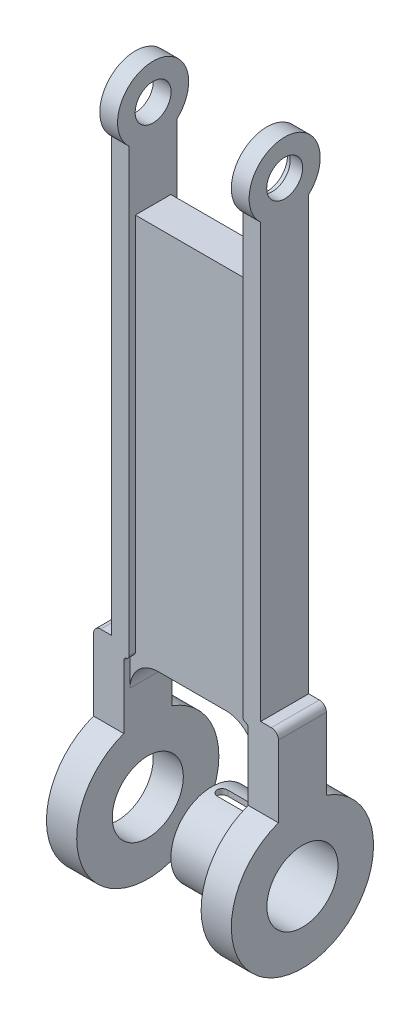
SolidWorks part; units mm, degrees
ref_plane "Alzado" through (0, 0, 0) normal (0, 0, 1) x (1, 0, 0)
ref_plane "Planta" through (0, 0, 0) normal (0, 1, 0) x (1, 0, 0)
ref_plane "Vista lateral" through (0, 0, 0) normal (1, 0, 0) x (0, 0, -1)
sketch "Croquis1" plane through (0, 0, 0) normal (0, 0, 1) x (1, 0, 0)
  line L0 (0, 0) -> (0, -143)
  line L1 (0, 0) -> (-1.6, 0)
  line L2 (-42, 0) -> (-42, -143)
  line L4 (-42, -35) -> (0, -35)
  line L5 (-42, -143) -> (0, -143)
  line L6 (-42, 0) -> (-37.4, 0)
  line L7 (-37.4, 0) -> (-37.4, -35)
  line L8 (-1.6, 0) -> (-1.6, -35)
  line L9 (-37.4, 0) -> (-42, 0)
  dimension "D1" = 42
extrude "Saliente-Extruir1" add sketch "Croquis1" against normal blind 10 contours L4 L5 region at (-21, -89, 0)
sketch "Croquis3" plane through (0, 0, 0) normal (0, 0, 1) x (1, 0, 0)
  line L0 (-47, -145) -> (-47, -160)
  line L1 (-47, -200) -> (-47, -180) construction
  line L2 (-47, -145) -> (-47, -141)
  line L4 (-47, -180) -> (-30.5, -180) construction
  line L5 (-42, -35) -> (-42, 0)
  line L6 (5, -143) -> (5, -200)
  line L7 (-47, -200) -> (-47, -180)
  line L8 (-30.5, -180) -> (-30.5, -143) construction
  line L9 (-42, -143) -> (0, -143) construction
  line L10 (-47, -180) -> (-47, -200)
  line L11 (-47, -180) -> (-47, -160)
  line L12 (-3.5, -151) -> (-3.5, -200)
  line L13 (-38.5, -200) -> (-38.5, -151)
  line L14 (5, -143) -> (5, -141)
  line L15 (-47, -200) -> (-38.5, -200)
  line L16 (-3.5, -200) -> (5, -200)
  line L17 (-45, -139) -> (-42, -139)
  line L18 (-42, -35) -> (-42, -143) construction
  line L19 (-30.5, -143) -> (-11.5, -143)
  line L20 (3, -139) -> (0, -139)
  line L21 (0, -35) -> (0, -143) construction
  line L22 (-30.5, -143) -> (-38.5, -143)
  line L23 (-38.5, -143) -> (-38.5, -151)
  line L24 (-30.5, -143) -> (-38.5, -143)
  arc A0 (5, -141) -> (3, -139) centre (3, -141) ccw
  arc A1 (-45, -139) -> (-47, -141) centre (-45, -141) ccw
  arc A2 (-11.5, -143) -> (-3.5, -151) centre (-11.5, -151) cw
  arc A3 (-38.5, -151) -> (-30.5, -143) centre (-30.5, -151) cw
  point P7 (5, -143)
  point P14 (10, -143)
  point P27 (-47, -143)
  point P29 (-49.26, -143)
  point P31 (7.26, -143)
  line M12 (-42, -35) -> (-42, -143)
  line M13 (-42, -143) -> (0, -143)
  line M14 (0, -143) -> (0, -35)
  dimension "D1" = 8.5
  dimension "D3" = 2
  dimension "D6" = 2
  dimension "D5" = 8
  dimension "D2" = 165
  dimension "D4" = 35
  dimension "D7" = 8.5
sketch "Croquis20" plane through (0, -35, 0) normal (0, 1, 0) x (1, 0, 0)
extrude "Saliente-Extruir2" add sketch "Croquis3" against normal blind 10 contours L17 A1 L2 L0 L11 L7 L15 L13 L23 M13 M12 | A2 L12 L16 L6 L14 A0 L20 M13 M14 region at (-42.813, -170.3435, 0) region at (0.6511, -169.665, 0)
sketch "Croquis21" plane through (0, 0, 0) normal (0, 0, 1) x (1, 0, 0)
  line L0 (-47, -145) -> (-47, -160)
  line L1 (-47, -200) -> (-47, -180) construction
  line L2 (-47, -145) -> (-47, -141)
  line L4 (-47, -180) -> (-30.5, -180) construction
  line L5 (-42, -35) -> (-42, 0)
  line L6 (5, -143) -> (5, -200)
  line L7 (-47, -200) -> (-47, -180)
  line L8 (-30.5, -180) -> (-30.5, -143) construction
  line L10 (-47, -180) -> (-47, -200)
  line L11 (-47, -180) -> (-47, -160)
  line L12 (-3.5, -151) -> (-3.5, -200)
  line L13 (-38.5, -200) -> (-38.5, -151)
  line L14 (5, -143) -> (5, -141)
  line L15 (-47, -200) -> (-38.5, -200)
  line L16 (-3.5, -200) -> (5, -200)
  line L17 (-45, -139) -> (-42, -139)
  line L19 (-30.5, -143) -> (-11.5, -143)
  line L20 (3, -139) -> (0, -139)
  line L22 (-30.5, -143) -> (-38.5, -143)
  line L23 (-38.5, -143) -> (-38.5, -151)
  line L24 (-30.5, -143) -> (-38.5, -143)
  arc A0 (5, -141) -> (3, -139) centre (3, -141) ccw
  arc A1 (-45, -139) -> (-47, -141) centre (-45, -141) ccw
  arc A2 (-11.5, -143) -> (-3.5, -151) centre (-11.5, -151) cw
  arc A3 (-38.5, -151) -> (-30.5, -143) centre (-30.5, -151) cw
  point P7 (5, -143)
  point P14 (10, -143)
  point P27 (-47, -143)
  point P29 (-49.26, -143)
  point P31 (7.26, -143)
  dimension "D1" = 8.5
  dimension "D3" = 2
  dimension "D6" = 2
  dimension "D5" = 8
  dimension "D4" = 35
  dimension "D7" = 8.5
extrude "Saliente-Extruir3" add sketch "Croquis21" against normal blind 10 contours L23 A3 L22 region at (-36.7131, -144.7869, 0)
sketch "Croquis22" plane through (0, 0, -10) normal (0, 0, -1) x (-1, 0, 0)
  line L0 (3.5, -156.8736) -> (3.5, -141.3338)
  line L1 (38.5, -155.5125) -> (38.5, -141.3338)
  line L2 (3.5, -151) -> (3.5, -200) construction
  line L3 (5, -139.3973) -> (5, -35)
  line L4 (42, -35) -> (0, -35) construction
  line L5 (0, -35) -> (0, -139) construction
  line L6 (5, -35) -> (0, -35)
  line L7 (38.5, -200) -> (38.5, -151) construction
  line L8 (37, -35) -> (37, -139.3973)
  line L9 (42, -35) -> (42, -139) construction
  line L10 (0, -35) -> (0, -139)
  line L11 (0, -139) -> (-3, -139)
  line L12 (45, -139) -> (42, -139) construction
  line L13 (47, -200) -> (47, -141) construction
  line L14 (47, -200) -> (38.5, -200) construction
  line L15 (3.5, -200) -> (-5, -200) construction
  line L16 (-5, -141) -> (-5, -200) construction
  line L17 (42, -35) -> (0, -35)
  line L18 (42, -35) -> (42, -139)
  line L19 (45, -139) -> (42, -139)
  line L20 (47, -200) -> (47, -141)
  line L21 (38.5, -200) -> (38.5, -151)
  line L22 (47, -200) -> (38.5, -200)
  line L23 (3.5, -200) -> (-5, -200)
  line L24 (-5, -141) -> (-5, -200)
  arc A0 (4.25, -140.3655) -> (3.5, -141.3338) centre (4.5, -141.3338) ccw
  arc A1 (4.25, -140.3655) -> (5, -139.3973) centre (4, -139.3973) ccw
  arc A2 (37.75, -140.3655) -> (37, -139.3973) centre (38, -139.3973) cw
  arc A3 (38.5, -141.3338) -> (37.75, -140.3655) centre (37.5, -141.3338) ccw
  arc A4 (47, -141) -> (45, -139) centre (45, -141) ccw construction
  arc A5 (-3, -139) -> (-5, -141) centre (-3, -141) ccw construction
  arc A6 (47, -141) -> (45, -139) centre (45, -141) ccw
  arc A7 (-3, -139) -> (-5, -141) centre (-3, -141) ccw
  line M10 (38.5, -151) -> (38.5, -200)
  line M11 (38.5, -200) -> (47, -200)
  line M12 (47, -200) -> (47, -141)
  arc M13 (47, -141) -> (45, -139) centre (45, -141) ccw
  line M14 (45, -139) -> (42, -139)
  line M15 (42, -139) -> (42, -35)
  line M16 (42, -35) -> (0, -35)
  line M17 (0, -35) -> (0, -139)
  line M18 (0, -139) -> (-3, -139)
  arc M19 (-3, -139) -> (-5, -141) centre (-3, -141) ccw
  line M20 (-5, -141) -> (-5, -200)
  line M21 (-5, -200) -> (3.5, -200)
  line M22 (3.5, -200) -> (3.5, -151)
  dimension "D2" = 1
  dimension "D3" = 1
  dimension "D5" = 1
  dimension "D6" = 1
  dimension "D1" = 5
  dimension "D4" = 5
extrude "Saliente-Extruir4" add sketch "Croquis22" along normal blind 1.75 contours A0 A1 L3 L0 M16 M17 M18 M19 M20 M21 M22 | A3 L1 L8 A2 M10 M11 M12 M13 M14 M15 M16 region at (-0.8883, -128.2038, -10) region at (-41.1117, -128.2038, -10)
sketch "Croquis24" plane through (0, 0, 0) normal (0, 0, 1) x (1, 0, 0)
  line L0 (-37, -35) -> (-37, -138.9269)
  line L1 (-42, -35) -> (0, -35) construction
  line L2 (-5, -35) -> (-5, -138.9269)
  line L3 (-42, -35) -> (-42, -139) construction
  line L4 (0, -35) -> (0, -139) construction
  line L5 (-38.5, -156.0308) -> (-38.5, -143.4351)
  line L6 (-38.5, -200) -> (-38.5, -151) construction
  line L7 (-3.5, -141.3338) -> (-3.5, -151) construction
  line L8 (-3.5, -151) -> (-3.5, -200) construction
  line L9 (-3.5, -151) -> (-3.5, -142.3338)
  line L10 (-37, -141.4986) -> (-37, -138.9269)
  line L11 (-5, -140.3973) -> (-5, -138.9269)
  line L12 (-3.5, -200) -> (5, -200) construction
  line L13 (5, -141) -> (5, -200) construction
  line L14 (3, -139) -> (0, -139) construction
  line L15 (-45, -139) -> (-42, -139) construction
  line L16 (-47, -200) -> (-47, -141) construction
  line L17 (-47, -200) -> (-38.5, -200) construction
  line L18 (-3.5, -151) -> (-3.5, -200)
  line L19 (-3.5, -200) -> (5, -200)
  line L20 (5, -141) -> (5, -200)
  line L21 (3, -139) -> (0, -139)
  line L22 (0, -35) -> (0, -139)
  line L23 (-42, -35) -> (-37, -35)
  line L24 (-42, -35) -> (-42, -139)
  line L25 (-45, -139) -> (-42, -139)
  line L26 (-47, -200) -> (-47, -141)
  line L27 (-47, -200) -> (-38.5, -200)
  line L28 (-38.5, -200) -> (-38.5, -151)
  line L29 (-5, -35) -> (0, -35)
  arc A0 (-4.25, -141.3655) -> (-5, -140.3973) centre (-4, -140.3973) cw
  arc A1 (-4.25, -141.3655) -> (-3.5, -142.3338) centre (-4.5, -142.3338) cw
  arc A2 (-37, -141.4986) -> (-37.75, -142.4669) centre (-38, -141.4986) cw
  arc A3 (-37.75, -142.4669) -> (-38.5, -143.4351) centre (-37.5, -143.4351) ccw
  arc A4 (5, -141) -> (3, -139) centre (3, -141) ccw construction
  arc A5 (-45, -139) -> (-47, -141) centre (-45, -141) ccw construction
  arc A6 (5, -141) -> (3, -139) centre (3, -141) ccw
  arc A7 (-45, -139) -> (-47, -141) centre (-45, -141) ccw
  point P28 (-37, -142.4986)
  line M6 (-3.5, -151) -> (-3.5, -200)
  line M7 (-3.5, -200) -> (5, -200)
  line M8 (5, -200) -> (5, -141)
  arc M9 (5, -141) -> (3, -139) centre (3, -141) ccw
  line M10 (3, -139) -> (0, -139)
  line M11 (0, -139) -> (0, -35)
  line M12 (0, -35) -> (-42, -35)
  line M13 (-42, -35) -> (-42, -139)
  line M14 (-42, -139) -> (-45, -139)
  arc M15 (-45, -139) -> (-47, -141) centre (-45, -141) ccw
  line M16 (-47, -141) -> (-47, -200)
  line M17 (-47, -200) -> (-38.5, -200)
  line M18 (-38.5, -200) -> (-38.5, -151)
  dimension "D3" = 1
  dimension "D4" = 1
  dimension "D5" = 1
  dimension "D6" = 1
  dimension "D1" = 5
  dimension "D2" = 5
extrude "Saliente-Extruir5" add sketch "Croquis24" along normal blind 1.75 contours A3 A2 L10 L0 L5 M12 M13 M14 M15 M16 M17 M18 | A0 A1 L9 L2 L11 M6 M7 M8 M9 M10 M11 M12 region at (-41.1016, -128.2438, 0) region at (-0.8931, -128.2221, 0)
ref_plane "Plano1" through (0, -35, 1.75) normal (0, 0, 1) x (1, 0, 0)
sketch "Croquis26" plane through (0, 0, 0) normal (0, 0, 1) x (1, 0, 0)
  line L4 (-42, -35) -> (-37, -35)
  line L5 (-42, -35) -> (-42, 0)
  line L6 (-42, 0) -> (-37, 0)
  line L7 (-37, -35) -> (-37, 0)
  line L8 (-5, -35) -> (0, -35)
  line L9 (-5, -35) -> (-5, 0)
  line L10 (-5, 0) -> (0, 0)
  line L11 (0, -35) -> (0, 0)
  dimension "D1" = 35
  dimension "D2" = 35
extrude "Saliente-Extruir6" add sketch "Croquis26" along normal up to surface (1.75 mm away) up to face at (-41.2164, -131.5986, 1.75)
sketch "Croquis27" plane through (0, 0, 0) normal (0, 0, -1) x (-1, 0, 0)
  line L1 (0, 0) -> (5, 0)
  line L2 (0, 0) -> (0, -35)
  line L3 (0, -35) -> (5, -35)
  line L4 (5, 0) -> (5, -35)
  line L5 (37, 0) -> (42, 0)
  line L6 (37, 0) -> (37, -35)
  line L7 (37, -35) -> (42, -35)
  line L8 (42, 0) -> (42, -35)
extrude "Saliente-Extruir7" add sketch "Croquis27" along normal up to surface (11.75 mm away) up to face at (-0.7836, -130.9682, -11.75)
sketch "Croquis28" plane through (-5, 0, 0) normal (-1, 0, 0) x (0, 0, 1)
  line L0 (-5, 0) -> (-5, -20) construction
  line L1 (1.75, 0) -> (-11.75, 0) construction
  line L2 (1.75, 0) -> (1.75, -140.3973) construction
  line L3 (1.75, 0) -> (1.75, -140.3973)
  line L4 (1.75, 0) -> (-11.75, 0)
  circle A0 centre (-5, -10) radius 10
  line M7 (1.75, -140.3973) -> (1.75, 0)
  line M8 (1.75, 0) -> (-11.75, 0)
  line M9 (-11.75, 0) -> (-11.75, -139.3973)
  dimension "D1" = 20
extrude "Cortar-Extruir3" cut sketch "Croquis28" against normal blind 99.75 and the other way through all contours A0 L4 M9 | A0 M7 M8 region at (-5, -0.7651, 0.1099) region at (-5, -0.7651, -10.1099)
extrude "Saliente-Extruir8" add sketch "Croquis28<5>" against normal up to surface (5 mm away) contours A0 M9 | L3 A0 region at (-5, -10, 3.07) region at (-5, -10, -13.07) up to face at (0, -70.1555, -5)
sketch "Croquis28<5>" plane through (-5, 0, 0) normal (-1, 0, 0) x (0, 0, 1) same geometry as "Croquis28"
sketch "Croquis29" plane through (-37, 0, 0) normal (1, 0, 0) x (0, 0, -1)
  line L0 (5, 0) -> (5, -20) construction
  arc A0 (11.75, -2.6218) -> (-1.75, -2.6218) centre (5, -10) ccw construction
  circle A1 centre (5, -10) radius 10
  dimension "D2" = 20
  dimension "D1" = 20
extrude "Saliente-Extruir9" add sketch "Croquis29" against normal up to surface (5 mm away) up to face at (-42, -70.1555, -5)
sketch "Croquis31" plane through (-38.5, 0, 0) normal (1, 0, 0) x (0, 0, -1)
  line L0 (5, -200) -> (5, -160) construction
  line L1 (11.75, -200) -> (-1.75, -200) construction
  line L2 (11.75, -200) -> (11.75, -141.3338) construction
  line L3 (-1.75, -200) -> (-1.75, -143.4351) construction
  line L4 (11.75, -198.8265) -> (11.75, -141.3338)
  line L5 (11.75, -200) -> (11.75, -141.3338)
  line L6 (-1.75, -198.8265) -> (-1.75, -143.4351)
  line L7 (11.75, -200) -> (-1.75, -200)
  line L8 (-1.75, -200) -> (-1.75, -143.4351)
  circle A0 centre (5, -180) radius 20
  line M5 (-1.75, -143.4351) -> (-1.75, -200)
  line M6 (-1.75, -200) -> (11.75, -200)
  line M7 (11.75, -200) -> (11.75, -141.3338)
  dimension "D2" = 40
  dimension "D1" = 40
extrude "Cortar-Extruir5" cut sketch "Croquis31" along normal through all both and the other way through all contours A0 M5 M6 | A0 L7 M7 region at (-38.5, -199.6498, -10.0726) region at (-38.5, -199.6498, 0.0726)
sketch "Croquis32" plane through (-38.5, 0, 0) normal (1, 0, 0) x (0, 0, -1)
  line L0 (5, -200) -> (5, -160) construction
  arc A0 (-1.75, -198.8265) -> (11.75, -198.8265) centre (5, -180) ccw construction
  circle A1 centre (5, -180) radius 20
  dimension "D1" = 40
extrude "Saliente-Extruir11" add sketch "Croquis32" against normal up to surface (8.5 mm away) up to face at (-47, -170.2066, -5)
sketch "Croquis33" plane through (-3.5, 0, 0) normal (-1, 0, 0) x (0, 0, 1)
  line L0 (-5, -200) -> (-5, -160) construction
  arc A0 (-11.75, -198.8265) -> (1.75, -198.8265) centre (-5, -180) ccw construction
  circle A1 centre (-5, -180) radius 20
  dimension "D1" = 40
extrude "Saliente-Extruir12" add sketch "Croquis33" against normal up to surface (8.5 mm away) up to face at (5, -170.2066, -5)
sketch "Croquis34" plane through (-42, 0, 0) normal (-1, 0, 0) x (0, 0, 1)
  circle A0 centre (-5, -10) radius 5.05
  dimension "D1" = 10.1
extrude "Cortar-Extruir6" cut sketch "Croquis34" against normal blind 90
sketch "Croquis39" plane through (-5, 0, 0) normal (-1, 0, 0) x (0, 0, 1)
  circle A0 centre (-5, -10) radius 5.78
  dimension "D1" = 11.56
extrude "Cortar-Extruir7" cut sketch "Croquis39" against normal blind 1.5
sketch "Croquis41" plane through (-38.5, 0, 0) normal (1, 0, 0) x (0, 0, -1)
  circle A0 centre (5, -180) radius 10
  dimension "D1" = 20
extrude "Cortar-Extruir8" cut sketch "Croquis41" against normal blind 43
sketch "Croquis42" plane through (5, 0, 0) normal (1, 0, 0) x (0, 0, -1)
  circle A0 centre (5, -180) radius 4
  dimension "D1" = 8
extrude "Cortar-Extruir9" cut sketch "Croquis42" against normal blind 27
sketch "Croquis43" plane through (5, 0, 0) normal (1, 0, 0) x (0, 0, -1)
  circle A0 centre (5, -180) radius 10
  dimension "D1" = 20
extrude "Cortar-Extruir10" cut sketch "Croquis43" against normal blind 12
sketch "Croquis45" plane through (-3.5, 0, 0) normal (-1, 0, 0) x (0, 0, 1)
  circle A0 centre (-5, -180) radius 11.5
  dimension "D1" = 23
extrude "Saliente-Extruir13" add sketch "Croquis45" along normal blind 17
fillet "Redondeo1" radius 2 1 edges at (-3.5, -191.5, -5)
sketch "Croquis46" plane through (-20.5, 0, 0) normal (-1, 0, 0) x (0, 0, 1)
  line L0 (-5, -180) -> (-5, -168.5) construction
  line L1 (-5, -180) -> (6.5, -180) construction
  line L2 (-5, -168.5) -> (-8, -168.5)
  line L3 (-5, -168.5) -> (-2, -168.5)
  line L4 (-8, -168.5) -> (-8, -167.7638)
  line L5 (-8, -167.7638) -> (-2, -167.7638)
  line L6 (-2, -167.7638) -> (-2, -168.5)
  line L7 (-8, -168.5) -> (-8, -168.9564)
  line L8 (-2, -168.5) -> (-2, -168.9564)
  circle A0 centre (-5, -180) radius 11.5 construction
  circle A1 centre (-5, -180) radius 11.5 construction
  circle A2 centre (-5, -180) radius 11.5
  circle M3 centre (-5, -180) radius 11.5
  dimension "D1" = 3
  dimension "D2" = 3
extrude "Saliente-Extruir14" add sketch "Croquis46" against normal blind 6 contours L2 L7 M3 | L8 L3 M3 | L6 L5 L4 L2 L3 region at (-20.5, -168.6191, -7.2526) region at (-20.5, -168.1319, -5) region at (-20.5, -168.6191, -2.7474)
sketch "Croquis48" plane through (-3.5, 0, 0) normal (1, 0, 0) x (0, 0, -1)
  circle A0 centre (5, -180) radius 10
extrude "Cortar-Extruir12" cut sketch "Croquis48" against normal blind 17
sketch "Croquis49" plane through (-20.5, 0, 0) normal (-1, 0, 0) x (0, 0, 1)
  line L0 (-8, -167.7638) -> (-2, -167.7638) construction
  line L1 (-8, -167.7638) -> (-2, -167.7638)
  line L2 (-8, -167.7638) -> (-8, -168.8982) construction
  line L3 (-8, -167.7638) -> (-8, -168.8982)
  line L4 (-2, -167.7638) -> (-2, -168.8982) construction
  line L5 (-2, -167.7638) -> (-2, -168.8982)
  circle A0 centre (-5, -180) radius 11.5 construction
  circle A1 centre (-5, -180) radius 11.5
  line M3 (-2, -168.8982) -> (-2, -167.7638)
  line M4 (-2, -167.7638) -> (-8, -167.7638)
  line M5 (-8, -167.7638) -> (-8, -168.8982)
sketch "Croquis50" plane through (-20.5, 0, 0) normal (-1, 0, 0) x (0, 0, 1)
  line L0 (-5, -168.5) -> (-5, -180) construction
  line L1 (-5, -180) -> (-16.5, -180) construction
  line L2 (-16.5, -180) -> (-16.5, -183)
  line L3 (-16.5, -180) -> (-16.5, -176.344)
  line L4 (-16.5, -176.344) -> (-17.164, -176.344)
  line L5 (-17.164, -176.344) -> (-17.164, -183)
  line L6 (-17.164, -183) -> (-16.5, -183)
  line L7 (-16.5, -183) -> (-16.1018, -183)
  line L8 (-16.5, -176.344) -> (-15.9034, -176.344)
  circle A0 centre (-5, -180) radius 11.5 construction
  circle A1 centre (-5, -180) radius 11.5 construction
  circle A2 centre (-5, -180) radius 11.5
  arc M3 (-8, -168.8982) -> (-2, -168.8982) centre (-5, -180) ccw
  dimension "D1" = 0.664
extrude "Saliente-Extruir16" add sketch "Croquis50" against normal blind 6 separate body contours L2 L7 M3 | L8 L3 M3 | L5 L6 L2 L3 L4 region at (-20.5, -182.2526, -16.3809) region at (-20.5, -179.672, -16.832) region at (-20.5, -177.2532, -16.3218)
sketch "Croquis51" plane through (0, 0, -17.164) normal (0, 0, -1) x (-1, 0, 0)
  line L0 (19, -180.1991) -> (20.5, -180.1991) construction
  line L2 (20.5, -176.344) -> (20.5, -183) construction
  line L3 (17.5, -180.1991) -> (8.5, -180.1991) construction
  line L4 (17.5, -181.6991) -> (8.5, -181.6991)
  line L5 (17.5, -178.6991) -> (8.5, -178.6991)
  arc A1 (17.5, -181.6991) -> (17.5, -178.6991) centre (17.5, -180.1991) ccw
  arc A2 (8.5, -178.6991) -> (8.5, -181.6991) centre (8.5, -180.1991) ccw
  point P5 (13, -180.1991)
  dimension "D2" = 3
  dimension "D1" = 1.5
  dimension "D3" = 9
extrude "Cortar-Extruir20" cut sketch "Croquis51" against normal blind 6
sketch "Croquis52" plane through (-20.5, 0, 0) normal (-1, 0, 0) x (0, 0, 1)
  line L0 (-17.164, -183) -> (-16.1018, -183) construction
  line L1 (-15.9034, -176.344) -> (-17.164, -176.344) construction
  line L2 (-17.164, -176.344) -> (-17.164, -183) construction
  line L3 (-17.164, -183) -> (-16.1018, -183)
  line L4 (-15.9034, -176.344) -> (-17.164, -176.344)
  line L5 (-17.164, -176.344) -> (-17.164, -183)
  arc A0 (-15.9034, -176.344) -> (-16.1018, -183) centre (-5, -180) ccw construction
  arc A1 (-15.9034, -176.344) -> (-16.1018, -183) centre (-5, -180) ccw
sketch "Croquis53" plane through (0, -167.7638, 0) normal (0, 1, 0) x (1, 0, 0)
  line L0 (-19, 5.0424) -> (-20.5, 5) construction
  line L2 (-8.4994, 5.0424) -> (-17.5, 5.0424) construction
  line L3 (-8.4994, 3.5424) -> (-17.5, 3.5424)
  line L4 (-8.4994, 6.5424) -> (-17.5, 6.5424)
  line L5 (-20.5, 16.5) -> (-20.5, -6.5) construction
  line L6 (-6.9994, 5.0424) -> (-5.5, 5) construction
  line L7 (-5.5, -6.5) -> (-5.5, 16.5) construction
  arc A1 (-8.4994, 3.5424) -> (-8.4994, 6.5424) centre (-8.4994, 5.0424) ccw
  arc A2 (-17.5, 6.5424) -> (-17.5, 3.5424) centre (-17.5, 5.0424) ccw
  point P4 (-12.9997, 5.0424)
  dimension "D2" = 3
  dimension "D3" = 1.5
extrude "Cortar-Extruir21" cut sketch "Croquis53" against normal blind 10
extrude "Cortar-Extruir22" cut sketch "Croquis49" against normal blind 13 contours A1 M3 M4 M5 region at (-20.5, -168.2059, -5)
extrude "Cortar-Extruir23" cut sketch "Croquis52" against normal blind 13
